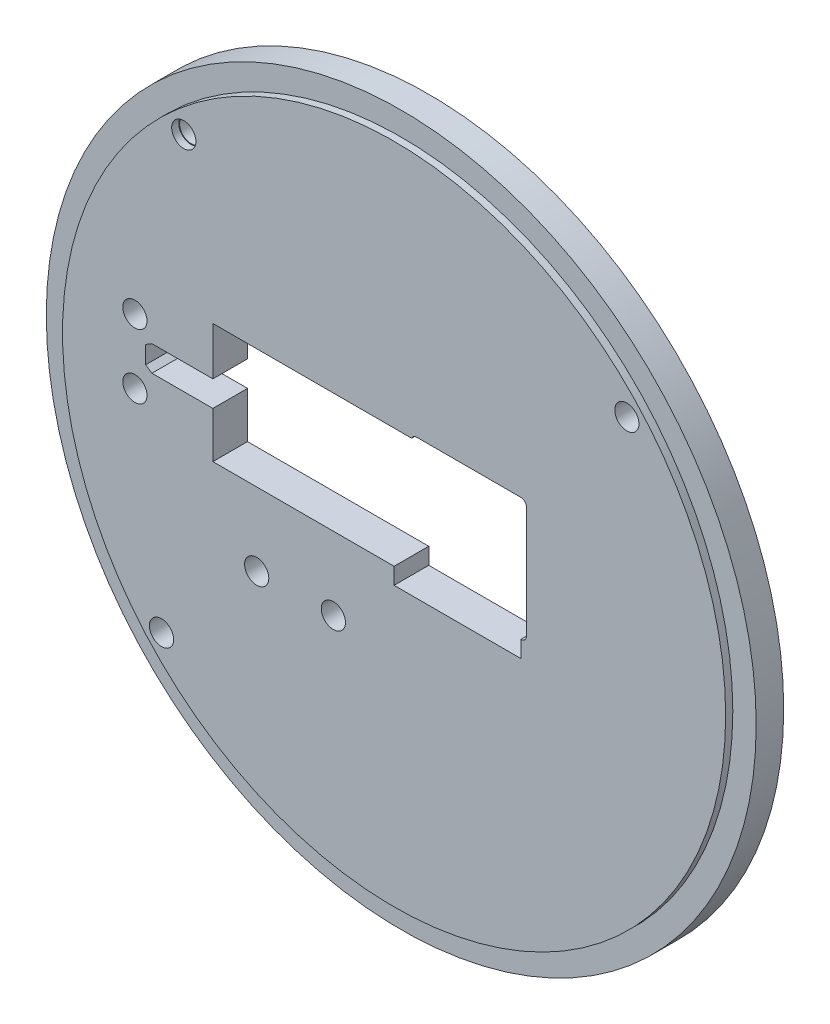
SolidWorks part; units mm, degrees
ref_plane "Piano frontale" through (0, 0, 0) normal (0, 0, 1) x (1, 0, 0)
ref_plane "Piano superiore" through (0, 0, 0) normal (0, 1, 0) x (1, 0, 0)
ref_plane "Piano destro" through (0, 0, 0) normal (1, 0, 0) x (0, 0, -1)
sketch "Schizzo1" plane through (0, 0, 0) normal (0, 0, 1) x (1, 0, 0)
  circle A0 centre (0, 0) radius 64.5
  circle A1 centre (0, 0) radius 60.25
extrude "Estrusione-Estrusione1" add sketch "Schizzo1" along normal blind 1.3 contours A1
extrude "Estrusione-Estrusione2" add sketch "Schizzo1<6>" against normal blind 5 separate body
sketch "Schizzo1<6>" plane through (0, 0, 0) normal (0, 0, 1) x (1, 0, 0) same geometry as "Schizzo1"
sketch "Schizzo2" plane through (0, 0, 0) normal (0, 0, -1) x (-1, 0, 0)
  circle A0 centre (0, 0) radius 60.25
extrude "Estrusione-Estrusione3" add sketch "Schizzo2" along normal blind 5
sketch "Schizzo4" plane through (0, 0, 0) normal (0, 0, 1) x (1, 0, 0)
  line L0 (-40.5912, 44.8621) -> (0, 0)
  line L1 (0, 0) -> (44.4249, 39.9216)
  line L2 (44.4249, 39.9216) -> (-44.8775, -40.5741)
  circle A0 centre (-38.216, 42.1859) radius 2.2
  circle A1 centre (42.2959, 38.0025) radius 2.2
  circle A2 centre (-42.2581, -38.213) radius 2.2
  circle A3 centre (0, 0) radius 3.8948
extrude "Taglio-Estrusione1" cut sketch "Schizzo4" along normal blind 22.55 contours A1 | A2 | A0
sketch "Schizzo5" plane through (0, 0, 0) normal (0, 0, 1) x (1, 0, 0)
  circle A0 centre (42.2959, 38.0025) radius 2.2
  circle A1 centre (-38.216, 42.1859) radius 2.0634
  circle A2 centre (-42.2581, -38.213) radius 2.2
extrude "Taglio-Estrusione2" cut sketch "Schizzo5" against normal through all
sketch "Schizzo6" plane through (0, 0, -5) normal (0, 0, -1) x (-1, 0, 0)
  circle A3 centre (-42.2959, 38.0025) radius 3.55
  circle A4 centre (38.216, 42.1859) radius 3.55
  circle A5 centre (42.2581, -38.213) radius 3.55
extrude "Taglio-Estrusione3" cut sketch "Schizzo6" against normal blind 3
sketch "Schizzo16" plane through (0, 0, 1.3) normal (0, 0, 1) x (1, 0, 0)
  line L0 (-32.9284, 14.986) -> (-25.1744, 14.986)
  line L1 (-25.1744, 14.986) -> (-25.1744, -0.4128)
  line L2 (-25.1744, -0.4128) -> (-8.0281, -0.4128)
  line L3 (-8.0281, -0.4128) -> (-6.936, 0.6793)
  line L4 (-6.936, 0.6793) -> (-6.936, 13.0429)
  line L5 (-4.8754, 15.1035) -> (3.1872, 15.1035)
  line L6 (4.1315, 15.7217) -> (23.0169, 15.7217)
  line L7 (24.0472, 14.6914) -> (24.0472, -5.6076)
  line L8 (23.0169, -6.6379) -> (-32.9284, -6.6379)
  line L9 (-32.9284, -6.6379) -> (-32.9284, 14.986)
  arc A0 (-6.936, 13.0429) -> (-4.8754, 15.1035) centre (-4.8754, 13.0429) cw
  arc A1 (3.1872, 15.1035) -> (4.1315, 15.7217) centre (4.1315, 14.6914) cw
  arc A3 (23.0169, 15.7217) -> (24.0472, 14.6914) centre (23.0169, 14.6914) cw
  arc A4 (24.0472, -5.6076) -> (23.0169, -6.6379) centre (23.0169, -5.6076) cw
extrude "Taglio-Estrusione4" cut sketch "Schizzo16" against normal through all
sketch "Schizzo18" plane through (0, 0, -5) normal (0, 0, -1) x (-1, 0, 0)
  line L0 (30.7286, 5.6534) -> (32.0006, 6.3878)
  line L1 (32.0006, 6.3878) -> (44.0006, 6.3878)
  line L2 (44.0006, 6.3878) -> (45.2055, 5.6643)
  line L3 (45.2055, 5.6643) -> (45.1561, 2.4759)
  line L4 (45.1561, 2.4759) -> (44.0006, 1.7378)
  line L5 (44.0006, 1.7378) -> (32.0006, 1.739)
  line L6 (32.0006, 1.739) -> (30.7286, 2.4734)
  line L7 (30.7286, 2.4734) -> (30.7286, 5.6534)
  line L8 (32.9284, 14.986) -> (32.0006, 6.3878)
  line L9 (32.9284, -6.6379) -> (32.0006, 1.739)
  line M39 (32.9284, 14.986) -> (32.9284, -6.6379)
extrude "Taglio-Estrusione5" cut sketch "Schizzo18" against normal through all contours L6 L5 L4 L3 L2 L1 L0 M39 region at (-38.9668, 4.0646, -5)
sketch "Schizzo19" plane through (0, 0, 1.3) normal (0, 0, 1) x (1, 0, 0)
  line L0 (-31.9323, 14.4923) -> (-50.9323, 14.4923)
  line L1 (-51.9323, 13.4923) -> (-51.9323, -5.4957)
  line L2 (-50.9323, -6.4957) -> (-31.9323, -6.4957)
  line L3 (-31.9323, -6.4957) -> (-31.9323, -25.4957)
  line L4 (-30.9323, -26.4957) -> (-5.0712, -26.4957)
  line L5 (-4.0712, -25.4957) -> (-4.0712, -6.4957)
  arc A0 (-50.9323, 14.4923) -> (-51.9323, 13.4923) centre (-50.9323, 13.4923) ccw
  arc A1 (-51.9323, -5.4957) -> (-50.9323, -6.4957) centre (-50.9323, -5.4957) ccw
  arc A2 (-31.9323, -25.4957) -> (-30.9323, -26.4957) centre (-30.9323, -25.4957) ccw
  arc A3 (-5.0712, -26.4957) -> (-4.0712, -25.4957) centre (-5.0712, -25.4957) ccw
  circle A4 centre (-47.097, 9.4988) radius 2.2
  circle A5 centre (-47.097, -2.2162) radius 2.2
  circle A6 centre (-24.9671, -19.916) radius 2.2
  circle A7 centre (-11.0365, -19.916) radius 2.2
  point P2 (0, 0)
  point P24 (0, 0)
extrude "Taglio-Estrusione6" cut sketch "Schizzo19" against normal through all contours A5 | A4 | A6 | A7 region at (-47.097, 9.4988, 1.3) region at (-47.097, -2.2162, 1.3) region at (-24.9671, -19.916, 1.3) region at (-11.0365, -19.916, 1.3)
sketch "Schizzo21" plane through (0, 0, -5) normal (0, 0, -1) x (-1, 0, 0)
  line L0 (0, 3.465) -> (0, -3.465) construction
  line L1 (-23.0169, -6.6379) -> (0, -6.6379)
  line L2 (-23.0169, -6.6379) -> (-23.0169, -9.6388)
  line L3 (-23.0169, -9.6388) -> (0, -9.6388)
  line L4 (0, -6.6379) -> (0, -9.6388)
  line L5 (-23.0169, -6.6379) -> (0, -9.6388) construction
  line L6 (-23.0169, -9.6388) -> (0, -6.6379) construction
  point P4 (-11.5084, -8.1384)
extrude "Taglio-Estrusione7" cut sketch "Schizzo21" against normal through all
sketch "Schizzo23" plane through (0, 0, -5) normal (0, 0, -1) x (-1, 0, 0)
  line L0 (3.465, 0) -> (-3.465, 0) construction
  line L5 (4.8754, 15.1035) -> (25.5501, 0) construction
  line L6 (4.8754, 0) -> (25.5501, 15.1035) construction
  line L8 (4.8754, 15.1035) -> (26.6731, 15.1035)
  line L9 (4.8754, 15.1035) -> (4.8754, -2.2276)
  line L10 (4.8754, -2.2276) -> (26.6731, -2.2276)
  line L11 (26.6731, 15.1035) -> (26.6731, -2.2276)
  line L12 (4.8754, 15.1035) -> (26.6731, -2.2276) construction
  line L13 (4.8754, -2.2276) -> (26.6731, 15.1035) construction
  point P4 (15.2128, 7.5517)
  point P12 (15.7742, 6.4379)
extrude "Taglio-Estrusione8" cut sketch "Schizzo23" against normal through all
sketch "Schizzo24" plane through (0, 0, 0) normal (0, 0, 1) x (1, 0, 0)
  line L1 (-32.9284, 14.986) -> (-26.6731, 14.986)
  line L2 (-32.9284, 14.986) -> (-32.9284, 15.1035)
  line L3 (-32.9284, 15.1035) -> (-26.6731, 15.1035)
  line L4 (-26.6731, 14.986) -> (-26.6731, 15.1035)
  line L5 (-32.9284, 14.986) -> (-26.6731, 15.1035) construction
  line L6 (-32.9284, 15.1035) -> (-26.6731, 14.986) construction
  point P4 (-29.8008, 15.0448)
extrude "Taglio-Estrusione9" cut sketch "Schizzo24" against normal through all
sketch "Schizzo25" plane through (0, 0, 1.3) normal (0, 0, 1) x (1, 0, 0)
  line L1 (-32.9284, 14.986) -> (-26.6731, 14.986)
  line L2 (-32.9284, 14.986) -> (-32.9284, 15.1035)
  line L3 (-32.9284, 15.1035) -> (-26.6731, 15.1035)
  line L4 (-26.6731, 14.986) -> (-26.6731, 15.1035)
  line L5 (-32.9284, 14.986) -> (-26.6731, 15.1035) construction
  line L6 (-32.9284, 15.1035) -> (-26.6731, 14.986) construction
  point P4 (-29.8008, 15.0448)
extrude "Taglio-Estrusione10" cut sketch "Schizzo25" against normal through all
